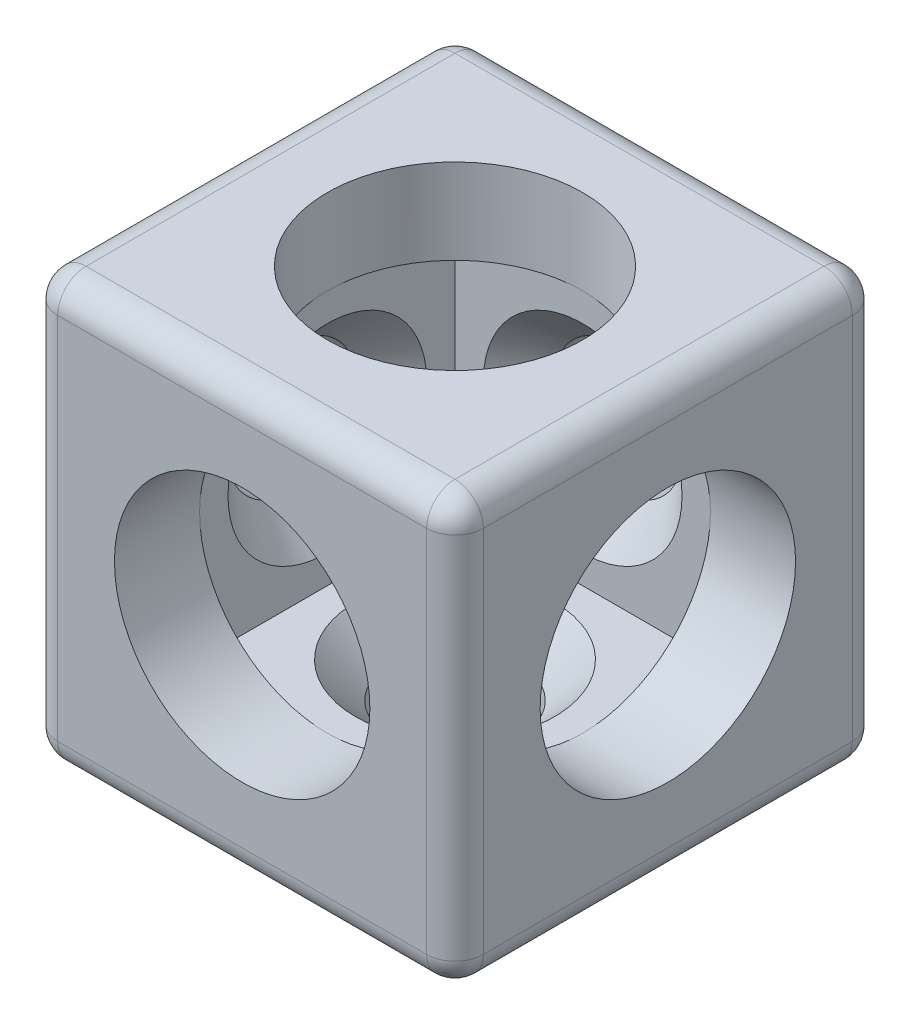
SolidWorks part; units mm, degrees
ref_plane "Front Plane" through (0, 0, 0) normal (0, 0, 1) x (1, 0, 0)
ref_plane "Top Plane" through (0, 0, 0) normal (0, 1, 0) x (1, 0, 0)
ref_plane "Right Plane" through (0, 0, 0) normal (1, 0, 0) x (0, 0, -1)
sketch "Sketch1" plane through (0, 0, 0) normal (0, 0, 1) x (1, 0, 0)
  line L1 (2, 0) -> (28, 0)
  line L2 (0, 2) -> (0, 28)
  line L3 (2, 30) -> (28, 30)
  line L4 (30, 2) -> (30, 28)
  arc A0 (0, 2) -> (2, 0) centre (2, 2) ccw
  arc A1 (28, 0) -> (30, 2) centre (28, 2) ccw
  arc A2 (30, 28) -> (28, 30) centre (28, 28) ccw
  arc A3 (0, 28) -> (2, 30) centre (2, 28) cw
  point P7 (0, 0)
  point P12 (30, 30)
  point P15 (0, 30)
  dimension "D3" = 2
  dimension "D1" = 30
  dimension "D2" = 30
extrude "Boss-Extrude1" add sketch "Sketch1" along normal blind 30
fillet "Fillet1" radius 2 16 edges at (15, 0, 0) (29.4142, 0.5858, 0) (30, 15, 0) (29.4142, 29.4142, 0) (15, 30, 0) (0.5858, 29.4142, 0) (0, 15, 0) (0.5858, 0.5858, 0) (0, 15, 30) (0.5858, 29.4142, 30) (15, 30, 30) (29.4142, 29.4142, 30) (30, 15, 30) (29.4142, 0.5858, 30) (15, 0, 30) (0.5858, 0.5858, 30)
shell "Shell2" thickness 6
sketch "Sketch3" plane through (0, 0, 30) normal (0, 0, 1) x (1, 0, 0)
  line L0 (15, 28) -> (15, 2) construction
  line L1 (28, 28) -> (2, 28) construction
  line L2 (2, 2) -> (28, 2) construction
  circle A0 centre (15, 15) radius 9
  dimension "D1" = 18
extrude "Cut-Extrude1" cut sketch "Sketch3" against normal blind 10 contours A0
sketch "Sketch4" plane through (30, 0, 0) normal (1, 0, 0) x (0, 0, -1)
  line L0 (-15, 28) -> (-15, 2) construction
  line L1 (-28, 28) -> (-2, 28) construction
  line L2 (-28, 2) -> (-2, 2) construction
  circle A0 centre (-15, 15) radius 9
  dimension "D1" = 18
extrude "Cut-Extrude2" cut sketch "Sketch4" against normal blind 10 contours A0
sketch "Sketch5" plane through (0, 30, 0) normal (0, 1, 0) x (1, 0, 0)
  line L0 (2, -15) -> (28, -15) construction
  line L1 (2, -28) -> (2, -2) construction
  line L2 (28, -28) -> (28, -2) construction
  circle A0 centre (15, -15) radius 9
  point P10 (15, -15)
  dimension "D1" = 18
extrude "Cut-Extrude3" cut sketch "Sketch5" against normal blind 10 contours A0
sketch "Sketch7" plane through (0, 0, 0) normal (-1, 0, 0) x (0, 0, 1)
  line L0 (15, 28) -> (15, 2) construction
  line L1 (28, 28) -> (2, 28) construction
  line L2 (28, 2) -> (2, 2) construction
  circle A0 centre (15, 15) radius 4.5
  dimension "D1" = 9
extrude "Cut-Extrude4" cut sketch "Sketch7" against normal blind 10
sketch "Sketch8" plane through (0, 0, 0) normal (0, 0, -1) x (-1, 0, 0)
  line L0 (-15, 28) -> (-15, 2) construction
  line L1 (-2, 28) -> (-28, 28) construction
  line L2 (-28, 2) -> (-2, 2) construction
  circle A0 centre (-15, 15) radius 4.5
  dimension "D1" = 9
extrude "Cut-Extrude5" cut sketch "Sketch8" against normal blind 10 contours A0
sketch "Sketch9" plane through (0, 0, 0) normal (0, -1, 0) x (1, 0, 0)
  line L0 (15, 2) -> (15, 28) construction
  line L1 (2, 2) -> (28, 2) construction
  line L2 (28, 28) -> (2, 28) construction
  circle A0 centre (15, 15) radius 4.5
  dimension "D1" = 9
extrude "Cut-Extrude6" cut sketch "Sketch9" against normal blind 10 contours A0
chamfer "Chamfer2" distance 2.5 angle 45 3 edges at (15, 6, 19.5) (19.5, 15, 6) (6, 15, 10.5)
